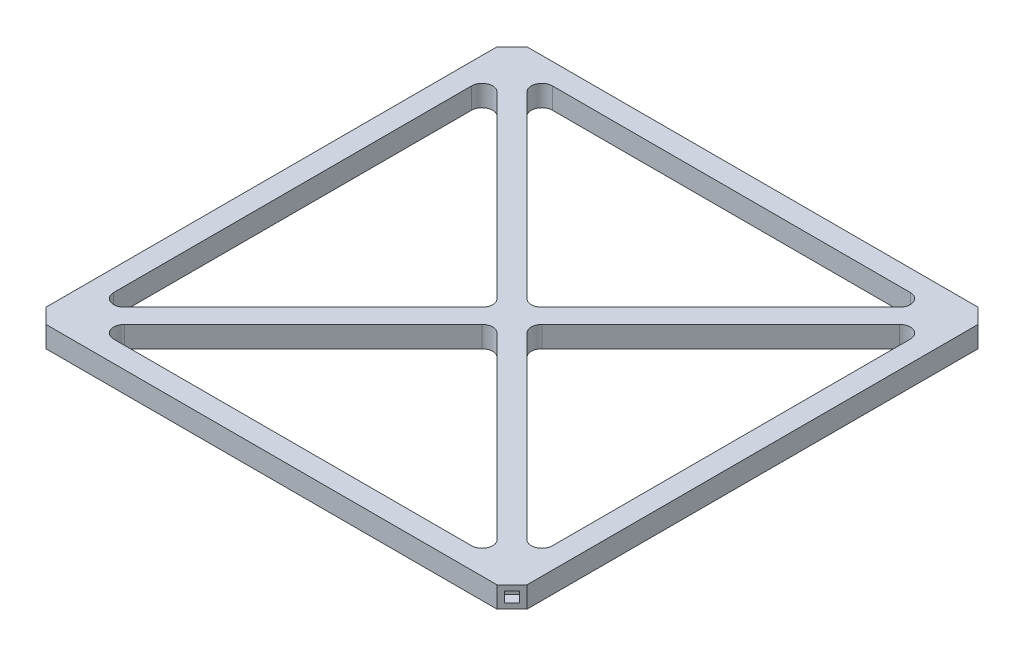
SolidWorks part; units mm, degrees
ref_plane "Front Plane" through (0, 0, 0) normal (0, 0, 1) x (1, 0, 0)
ref_plane "Top Plane" through (0, 0, 0) normal (0, 1, 0) x (1, 0, 0)
ref_plane "Right Plane" through (0, 0, 0) normal (1, 0, 0) x (0, 0, -1)
sketch "Sketch1" plane through (0, 0, 0) normal (0, 1, 0) x (1, 0, 0)
  line L0 (213.5462, 227.6884) -> (227.6884, 213.5462)
  line L1 (213.5462, 227.6884) -> (-213.5462, 227.6884)
  line L2 (-227.6884, 213.5462) -> (-227.6884, -213.5462)
  line L3 (-213.5462, -227.6884) -> (213.5462, -227.6884)
  line L4 (227.6884, -213.5462) -> (227.6884, 213.5462)
  line L5 (227.6884, -213.5462) -> (213.5462, -227.6884)
  line L6 (-213.5462, -227.6884) -> (-227.6884, -213.5462)
  line L7 (-227.6884, 213.5462) -> (-213.5462, 227.6884)
  line L8 (0, 0) -> (263.8431, 263.8431) construction
  line L9 (0, 0) -> (248.38, -248.38) construction
  line L10 (21.2132, 7.0711) -> (190.6173, 176.4752)
  line L11 (207.6884, 169.4041) -> (207.6884, -169.4041)
  line L12 (190.6173, -176.4752) -> (21.2132, -7.0711)
  line L13 (7.0711, -21.2132) -> (176.4752, -190.6173)
  line L14 (-176.4752, -190.6173) -> (-7.0711, -21.2132)
  line L15 (169.4041, -207.6884) -> (-169.4041, -207.6884)
  line L16 (-21.2132, -7.0711) -> (-190.6173, -176.4752)
  line L17 (-190.6173, 176.4752) -> (-21.2132, 7.0711)
  line L18 (-207.6884, -169.4041) -> (-207.6884, 169.4041)
  line L19 (-7.0711, 21.2132) -> (-176.4752, 190.6173)
  line L20 (176.4752, 190.6173) -> (7.0711, 21.2132)
  line L21 (-169.4041, 207.6884) -> (169.4041, 207.6884)
  circle A0 centre (0, 0) radius 227.6884 construction
  arc A1 (21.2132, -7.0711) -> (21.2132, 7.0711) centre (28.2843, 0) cw
  arc A2 (190.6173, 176.4752) -> (207.6884, 169.4041) centre (197.6884, 169.4041) cw
  arc A3 (207.6884, -169.4041) -> (190.6173, -176.4752) centre (197.6884, -169.4041) cw
  arc A4 (-169.4041, -207.6884) -> (-176.4752, -190.6173) centre (-169.4041, -197.6884) cw
  arc A5 (176.4752, -190.6173) -> (169.4041, -207.6884) centre (169.4041, -197.6884) cw
  arc A6 (-7.0711, -21.2132) -> (7.0711, -21.2132) centre (0, -28.2843) cw
  arc A7 (-207.6884, 169.4041) -> (-190.6173, 176.4752) centre (-197.6884, 169.4041) cw
  arc A8 (-190.6173, -176.4752) -> (-207.6884, -169.4041) centre (-197.6884, -169.4041) cw
  arc A9 (-21.2132, 7.0711) -> (-21.2132, -7.0711) centre (-28.2843, 0) cw
  arc A10 (169.4041, 207.6884) -> (176.4752, 190.6173) centre (169.4041, 197.6884) cw
  arc A11 (-176.4752, 190.6173) -> (-169.4041, 207.6884) centre (-169.4041, 197.6884) cw
  arc A12 (7.0711, 21.2132) -> (-7.0711, 21.2132) centre (0, 28.2843) cw
  point P18 (0, 0)
  point P55 (0, 0)
  dimension "D1" = 312
  dimension "D7" = 10
  dimension "D2" = 4
  dimension "D3" = 20
  dimension "D4" = 10
  dimension "D5" = 20
  dimension "D6" = 10
  dimension "D8" = 4
extrude "Boss-Extrude1" add sketch "Sketch1" along normal blind 20
sketch "Sketch3" plane through (220.6173, 0, -220.6173) normal (0.7071, 0, -0.7071) x (-0.7071, 0, -0.7071)
  line L0 (-10, 0) -> (10, 0) construction
  line L1 (5, 15) -> (-5, 15)
  line L2 (-5, 15) -> (-5, 5)
  line L3 (-5, 5) -> (5, 5)
  line L4 (5, 5) -> (5, 15)
  line L5 (10, 20) -> (10, 0) construction
  circle A0 centre (0, 10) radius 5 construction
  dimension "D1" = 10
  dimension "D2" = 5
  dimension "D3" = 5
extrude "Cut-Extrude1" cut sketch "Sketch3" against normal blind 10
ref_axis "Axis1" through (0, -1, 0) along (0, 1, 0)
pattern_circular "CirPattern1" count 4 over 360 about axis through (0, -1, 0) along (0, 1, 0) of "Cut-Extrude1"
